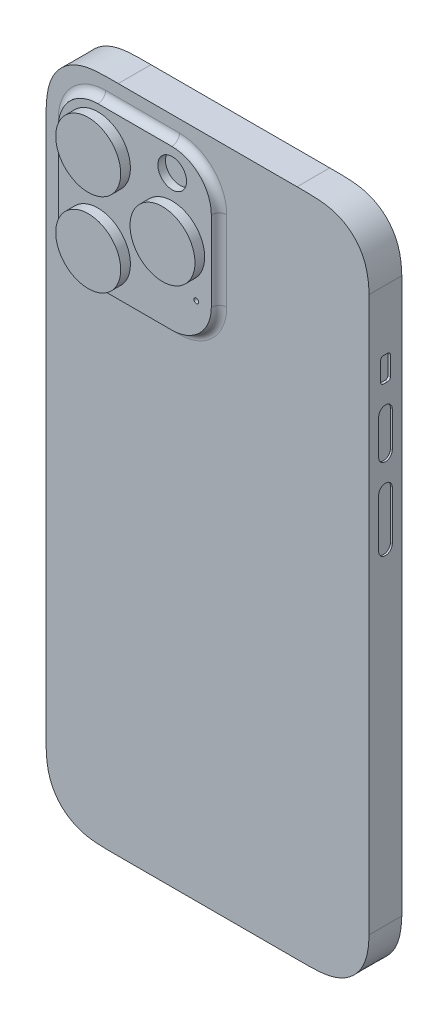
SolidWorks part; units mm, degrees
ref_plane "前视基准面" through (0, 0, 0) normal (0, 0, 1) x (1, 0, 0)
ref_plane "上视基准面" through (0, 0, 0) normal (0, 1, 0) x (1, 0, 0)
ref_plane "右视基准面" through (0, 0, 0) normal (1, 0, 0) x (0, 0, -1)
other "Configuration Table"
sketch "草图1" plane through (0, 0, 0) normal (0, 0, 1) x (1, 0, 0)
  line L0 (-34.5301, 57.507) -> (-34.5301, 50057.507) construction
  line L1 (-73.3201, 137.862) -> (4.2599, 137.862)
  line L2 (-73.3201, 137.862) -> (-73.3201, -22.848)
  line L3 (-73.3201, -22.848) -> (4.2599, -22.848)
  line L4 (4.2599, 137.862) -> (4.2599, -22.848)
  line L5 (-73.3201, 137.862) -> (4.2599, -22.848) construction
  line L6 (-73.3201, -22.848) -> (4.2599, 137.862) construction
  line L7 (-34.5301, 57.507) -> (-50034.5301, 57.507) construction
  spline S0 degree 3 poles (-73.3201, 122.312) (-73.3816, 125.2822) (-73.0975, 130.133) (-69.278, 135.1034) (-63.7712, 138.0734) (-58.9886, 137.839) (-56.0001, 137.862) knots 0 0 0 0 0.333631 0.499509 0.665643 1 1 1 1
  spline S1 degree 3 poles (4.2599, 122.312) (4.3213, 125.2822) (4.0372, 130.133) (0.2177, 135.1034) (-5.2891, 138.0734) (-10.0717, 137.839) (-13.0601, 137.862) knots 0 0 0 0 0.333631 0.499509 0.665643 1 1 1 1
  spline S2 degree 3 poles (-73.3201, -7.298) (-73.3816, -10.2683) (-73.0975, -15.119) (-69.278, -20.0894) (-63.7712, -23.0594) (-58.9886, -22.825) (-56.0001, -22.848) knots 0 0 0 0 0.333631 0.499509 0.665643 1 1 1 1
  spline S3 degree 3 poles (4.2599, -7.298) (4.3213, -10.2683) (4.0372, -15.119) (0.2177, -20.0894) (-5.2891, -23.0594) (-10.0717, -22.825) (-13.0601, -22.848) knots 0 0 0 0 0.333631 0.499509 0.665643 1 1 1 1
  point P0 (-34.5301, 57.507)
  point P8 (-34.5301, -22.848)
  dimension "D1" = 80.355
  dimension "D2" = 38.79
  dimension "D3" = 0.06
  dimension "D4" = 0.81
  dimension "D5" = 3.01
  dimension "D6" = 6.6
  dimension "D7" = 10.98
  dimension "D8" = 15.55
  dimension "D9" = 0.21
  dimension "D10" = 1.47
  dimension "D11" = 4.25
  dimension "D12" = 8.23
  dimension "D13" = 12.74
  dimension "D14" = 17.32
extrude "凸台-拉伸1" add sketch "草图1" along normal blind 7.85 contours S3 L4 S1 L1 S0 L2 S2 L3 region at (-34.5301, 57.507, 0)
sketch "草图2" plane through (0, 0, 0) normal (0, 0, 1) x (1, 0, 0)
  line L8 (3.2099, -9.0739) -> (3.2099, 124.0879)
  line L9 (-13.0601, 136.812) -> (-55.9921, 136.812)
  line L10 (-72.2701, 124.0879) -> (-72.2701, -9.0739)
  line L11 (-56.0001, -21.798) -> (-13.0682, -21.798)
  line L12 (3.2099, -9.0739) -> (3.2099, 124.0879)
  line L13 (-13.0601, 136.812) -> (-55.9921, 136.812)
  line L14 (-72.2701, 124.0879) -> (-72.2701, -9.0739)
  line L15 (-56.0001, -21.798) -> (-13.0682, -21.798)
  spline S8 degree 3 poles (-29.2466, -4019.9995) (-101.414, 29.9981) (-54.9704, -22.4333) (-9.0595, -21.7736) (-8.0573, -21.7337) (-6.0612, -21.501) (-5.0826, -21.3093) (-3.9015, -20.9066) (-3.6673, -20.8181) (-3.2033, -20.6244) (-2.973, -20.5189) (-2.2993, -20.1818) (-1.8694, -19.9282) (-1.0497, -19.3608) (-0.6602, -19.0466) (0.0745, -18.3515) (0.4109, -17.9801) (1.0253, -17.1947) (1.3034, -16.7803) (1.6761, -16.1257) (1.7933, -15.9009) (2.0092, -15.4457) (2.1083, -15.2152) (2.3817, -14.5156) (2.5321, -14.0387) (2.7815, -13.0678) (2.8807, -12.5723) (10.7356, 37.6797) (-191.2997, 108.2854) (3993.0103, -257.0084) knots -5.47769 -5.47769 -5.47769 -5.47769 0.125 0.125 0.25 0.25 0.375 0.375 0.40625 0.40625 0.4375 0.4375 0.5 0.5 0.5625 0.5625 0.625 0.625 0.6875 0.6875 0.71875 0.71875 0.75 0.75 0.8125 0.8125 0.875 0.875 7.135418 7.135418 7.135418 7.135418 only from (-13.0682, -21.798) to (3.2099, -9.0739)
  spline S9 degree 3 poles (3960.2276, 690.8908) (-194.8572, -12.8142) (10.7783, 76.533) (2.8113, 128.0401) (2.5814, 129.0045) (2.1288, 130.1799) (2.0294, 130.4142) (1.8154, 130.8709) (1.7004, 131.0942) (1.3319, 131.7492) (1.0553, 132.1662) (0.44, 132.9606) (0.0985, 133.3401) (-0.6285, 134.0332) (-1.0161, 134.349) (-1.6319, 134.779) (-1.8429, 134.915) (-2.276, 135.1729) (-2.4989, 135.295) (-3.1751, 135.6354) (-3.6378, 135.8295) (-4.5859, 136.1552) (-5.0715, 136.286) (-6.0615, 136.4956) (-6.5586, 136.573) (-8.0523, 136.7473) (-9.0524, 136.7873) (-54.9551, 137.4531) (-102.8249, 84.8062) (77.7594, 4133.9226) knots -6.328874 -6.328874 -6.328874 -6.328874 0.125 0.125 0.25 0.25 0.28125 0.28125 0.3125 0.3125 0.375 0.375 0.4375 0.4375 0.5 0.5 0.53125 0.53125 0.5625 0.5625 0.625 0.625 0.6875 0.6875 0.75 0.75 0.875 0.875 6.479402 6.479402 6.479402 6.479402 only from (3.2099, 124.0879) to (-13.0601, 136.812)
  spline S10 degree 3 poles (-39.8137, 4135.0135) (32.3537, 85.0159) (-14.0899, 137.4473) (-60.0008, 136.7875) (-61.003, 136.7477) (-62.9991, 136.515) (-63.9777, 136.3233) (-65.1588, 135.9206) (-65.393, 135.8321) (-65.857, 135.6384) (-66.0873, 135.5329) (-66.761, 135.1958) (-67.1909, 134.9422) (-68.0106, 134.3747) (-68.4001, 134.0605) (-69.1348, 133.3655) (-69.4712, 132.9941) (-70.0856, 132.2087) (-70.3637, 131.7943) (-70.7364, 131.1396) (-70.8536, 130.9149) (-71.0695, 130.4597) (-71.1686, 130.2292) (-71.442, 129.5296) (-71.5924, 129.0527) (-71.8418, 128.0818) (-71.941, 127.5863) (-79.7959, 77.3343) (122.2394, 6.7286) (-4062.0706, 372.0224) knots -5.47769 -5.47769 -5.47769 -5.47769 0.125 0.125 0.25 0.25 0.375 0.375 0.40625 0.40625 0.4375 0.4375 0.5 0.5 0.5625 0.5625 0.625 0.625 0.6875 0.6875 0.71875 0.71875 0.75 0.75 0.8125 0.8125 0.875 0.875 7.135418 7.135418 7.135418 7.135418 only from (-55.9921, 136.812) to (-72.2701, 124.0879)
  spline S11 degree 3 poles (-4029.2879, -575.8768) (125.7969, 127.8282) (-79.8386, 38.481) (-71.8716, -13.0261) (-71.6417, -13.9905) (-71.1891, -15.1659) (-71.0897, -15.4002) (-70.8757, -15.857) (-70.7607, -16.0803) (-70.3922, -16.7352) (-70.1156, -17.1522) (-69.5003, -17.9466) (-69.1588, -18.3261) (-68.4318, -19.0192) (-68.0442, -19.335) (-67.4284, -19.765) (-67.2174, -19.901) (-66.7843, -20.1589) (-66.5614, -20.281) (-65.8852, -20.6214) (-65.4224, -20.8155) (-64.4744, -21.1412) (-63.9888, -21.2721) (-62.9988, -21.4816) (-62.5017, -21.559) (-61.008, -21.7333) (-60.0079, -21.7733) (-14.1052, -22.4391) (33.7646, 30.2078) (-146.8197, -4018.9087) knots -6.328874 -6.328874 -6.328874 -6.328874 0.125 0.125 0.25 0.25 0.28125 0.28125 0.3125 0.3125 0.375 0.375 0.4375 0.4375 0.5 0.5 0.53125 0.53125 0.5625 0.5625 0.625 0.625 0.6875 0.6875 0.75 0.75 0.875 0.875 6.479402 6.479402 6.479402 6.479402 only from (-72.2701, -9.0739) to (-56.0001, -21.798)
  spline S12 degree 3 poles (-13.0682, -21.798) (-12.0661, -21.7903) (-11.0634, -21.8023) (-9.0595, -21.7736) (-8.0573, -21.7337) (-6.0612, -21.501) (-5.0826, -21.3093) (-3.9015, -20.9066) (-3.6673, -20.8181) (-3.2033, -20.6244) (-2.973, -20.5189) (-2.2993, -20.1818) (-1.8694, -19.9282) (-1.0497, -19.3608) (-0.6602, -19.0466) (0.0745, -18.3515) (0.4109, -17.9801) (1.0253, -17.1947) (1.3034, -16.7803) (1.6761, -16.1257) (1.7933, -15.9009) (2.0092, -15.4457) (2.1083, -15.2152) (2.3817, -14.5156) (2.5321, -14.0387) (2.7815, -13.0678) (2.8807, -12.5723) (3.1136, -11.0821) (3.1853, -10.0803) (3.2099, -9.0739) knots 0 0 0 0 0.125 0.125 0.25 0.25 0.375 0.375 0.40625 0.40625 0.4375 0.4375 0.5 0.5 0.5625 0.5625 0.625 0.625 0.6875 0.6875 0.71875 0.71875 0.75 0.75 0.8125 0.8125 0.875 0.875 1 1 1 1
  spline S13 degree 3 poles (3.2099, 124.0879) (3.1854, 125.0896) (3.1141, 126.0828) (2.8113, 128.0401) (2.5814, 129.0045) (2.1288, 130.1799) (2.0294, 130.4142) (1.8154, 130.8709) (1.7004, 131.0942) (1.3319, 131.7492) (1.0553, 132.1662) (0.44, 132.9606) (0.0985, 133.3401) (-0.6285, 134.0332) (-1.0161, 134.349) (-1.6319, 134.779) (-1.8429, 134.915) (-2.276, 135.1729) (-2.4989, 135.295) (-3.1751, 135.6354) (-3.6378, 135.8295) (-4.5859, 136.1552) (-5.0715, 136.286) (-6.0615, 136.4956) (-6.5586, 136.573) (-8.0523, 136.7473) (-9.0524, 136.7873) (-11.0553, 136.8164) (-12.0583, 136.8044) (-13.0601, 136.812) knots 0 0 0 0 0.125 0.125 0.25 0.25 0.28125 0.28125 0.3125 0.3125 0.375 0.375 0.4375 0.4375 0.5 0.5 0.53125 0.53125 0.5625 0.5625 0.625 0.625 0.6875 0.6875 0.75 0.75 0.875 0.875 1 1 1 1
  spline S14 degree 3 poles (-55.9921, 136.812) (-56.9942, 136.8043) (-57.9969, 136.8163) (-60.0008, 136.7875) (-61.003, 136.7477) (-62.9991, 136.515) (-63.9777, 136.3233) (-65.1588, 135.9206) (-65.393, 135.8321) (-65.857, 135.6384) (-66.0873, 135.5329) (-66.761, 135.1958) (-67.1909, 134.9422) (-68.0106, 134.3747) (-68.4001, 134.0605) (-69.1348, 133.3655) (-69.4712, 132.9941) (-70.0856, 132.2087) (-70.3637, 131.7943) (-70.7364, 131.1396) (-70.8536, 130.9149) (-71.0695, 130.4597) (-71.1686, 130.2292) (-71.442, 129.5296) (-71.5924, 129.0527) (-71.8418, 128.0818) (-71.941, 127.5863) (-72.1739, 126.0961) (-72.2456, 125.0943) (-72.2701, 124.0879) knots 0 0 0 0 0.125 0.125 0.25 0.25 0.375 0.375 0.40625 0.40625 0.4375 0.4375 0.5 0.5 0.5625 0.5625 0.625 0.625 0.6875 0.6875 0.71875 0.71875 0.75 0.75 0.8125 0.8125 0.875 0.875 1 1 1 1
  spline S15 degree 3 poles (-72.2701, -9.0739) (-72.2457, -10.0756) (-72.1744, -11.0688) (-71.8716, -13.0261) (-71.6417, -13.9905) (-71.1891, -15.1659) (-71.0897, -15.4002) (-70.8757, -15.857) (-70.7607, -16.0803) (-70.3922, -16.7352) (-70.1156, -17.1522) (-69.5003, -17.9466) (-69.1588, -18.3261) (-68.4318, -19.0192) (-68.0442, -19.335) (-67.4284, -19.765) (-67.2174, -19.901) (-66.7843, -20.1589) (-66.5614, -20.281) (-65.8852, -20.6214) (-65.4224, -20.8155) (-64.4744, -21.1412) (-63.9888, -21.2721) (-62.9988, -21.4816) (-62.5017, -21.559) (-61.008, -21.7333) (-60.0079, -21.7733) (-58.005, -21.8024) (-57.002, -21.7904) (-56.0001, -21.798) knots 0 0 0 0 0.125 0.125 0.25 0.25 0.28125 0.28125 0.3125 0.3125 0.375 0.375 0.4375 0.4375 0.5 0.5 0.53125 0.53125 0.5625 0.5625 0.625 0.625 0.6875 0.6875 0.75 0.75 0.875 0.875 1 1 1 1
  dimension "D1" = 1.05
extrude "切除-拉伸1" cut sketch "草图2" along normal blind 0.001 contours S12 L12 S13 L13 S14 L14 S15 L15
sketch "草图5" plane through (0, 0, 0) normal (0, 0, 1) x (1, 0, 0)
  line L8 (-56.0001, -18.613) -> (-13.0927, -18.6131)
  line L9 (-69.0851, 124.048) -> (-69.0851, -9.034)
  line L10 (-13.0602, 133.627) -> (-55.9676, 133.6271)
  line L11 (0.0249, -9.034) -> (0.0249, 124.048)
  line L12 (-56.0001, -18.613) -> (-13.0927, -18.6131)
  line L13 (-69.0851, 124.048) -> (-69.0851, -9.034)
  line L14 (-13.0602, 133.627) -> (-55.9676, 133.6271)
  line L15 (0.0249, -9.034) -> (0.0249, 124.048)
  spline S8 degree 3 poles (-4048.1363, -398.9785) (99.0671, 98.1446) (-75.1087, 31.6027) (-68.8413, -11.8028) (-68.7699, -12.1936) (-68.5846, -12.9696) (-68.4699, -13.3554) (-68.1899, -14.0991) (-68.023, -14.4587) (-67.625, -15.1486) (-67.3935, -15.4811) (-66.8857, -16.0919) (-66.6081, -16.3739) (-66.0012, -16.8869) (-65.6691, -17.1194) (-64.9804, -17.5224) (-64.6222, -17.6955) (-63.8797, -17.9882) (-63.4932, -18.1067) (-62.3333, -18.385) (-61.5491, -18.4789) (-59.9714, -18.5898) (-59.1772, -18.6044) (-13.5653, -18.8647) (31.3557, 15.1942) (64.0257, -4014.9279) knots -6.720849 -6.720849 -6.720849 -6.720849 0.125 0.125 0.1875 0.1875 0.25 0.25 0.3125 0.3125 0.375 0.375 0.4375 0.4375 0.5 0.5 0.5625 0.5625 0.625 0.625 0.75 0.75 0.875 0.875 7.928456 7.928456 7.928456 7.928456 only from (-69.0851, -9.034) to (-56.0001, -18.613)
  spline S9 degree 3 poles (-267.9824, 4126.1525) (34.1476, 101.67) (-13.4853, 133.8486) (-59.1098, 133.6192) (-59.8944, 133.606) (-61.4569, 133.5021) (-62.235, 133.4138) (-63.3907, 133.1489) (-63.7758, 133.0368) (-64.5324, 132.7496) (-64.8959, 132.5794) (-65.5921, 132.1835) (-65.9263, 131.9565) (-66.5518, 131.4416) (-66.836, 131.1593) (-67.3528, 130.5495) (-67.5865, 130.2213) (-67.9976, 129.5233) (-68.1694, 129.1604) (-68.4563, 128.4115) (-68.5727, 128.0245) (-68.763, 127.24) (-68.8365, 126.845) (-75.1574, 83.5753) (99.1977, 18.5223) (-4050.7998, 484.5064) knots -7.011508 -7.011508 -7.011508 -7.011508 0.125 0.125 0.25 0.25 0.375 0.375 0.4375 0.4375 0.5 0.5 0.5625 0.5625 0.625 0.625 0.6875 0.6875 0.75 0.75 0.8125 0.8125 0.875 0.875 7.627543 7.627543 7.627543 7.627543 only from (-55.9676, 133.6271) to (-69.0851, 124.048)
  spline S10 degree 3 poles (3979.076, 513.9925) (-168.1274, 16.8694) (6.0484, 83.4112) (-0.219, 126.8168) (-0.2904, 127.2076) (-0.4757, 127.9836) (-0.5904, 128.3693) (-0.8704, 129.1131) (-1.0373, 129.4727) (-1.4353, 130.1626) (-1.6668, 130.495) (-2.1746, 131.1058) (-2.4522, 131.3879) (-3.0591, 131.9009) (-3.3912, 132.1334) (-4.0799, 132.5364) (-4.4381, 132.7095) (-5.1806, 133.0022) (-5.5671, 133.1207) (-6.727, 133.399) (-7.5112, 133.4929) (-9.0889, 133.6038) (-9.8831, 133.6184) (-55.495, 133.8787) (-100.416, 99.8198) (-133.086, 4129.9419) knots -6.720849 -6.720849 -6.720849 -6.720849 0.125 0.125 0.1875 0.1875 0.25 0.25 0.3125 0.3125 0.375 0.375 0.4375 0.4375 0.5 0.5 0.5625 0.5625 0.625 0.625 0.75 0.75 0.875 0.875 7.928456 7.928456 7.928456 7.928456 only from (0.0249, 124.048) to (-13.0602, 133.627)
  spline S11 degree 3 poles (198.9221, -4011.1385) (-103.2079, 13.344) (-55.575, -18.8346) (-9.9505, -18.6052) (-9.1659, -18.592) (-7.6034, -18.4881) (-6.8253, -18.3998) (-5.6696, -18.1349) (-5.2845, -18.0228) (-4.5279, -17.7357) (-4.1644, -17.5654) (-3.4682, -17.1695) (-3.134, -16.9426) (-2.5085, -16.4276) (-2.2243, -16.1453) (-1.7075, -15.5356) (-1.4738, -15.2074) (-1.0627, -14.5093) (-0.8909, -14.1464) (-0.604, -13.3975) (-0.4876, -13.0105) (-0.2973, -12.226) (-0.2238, -11.831) (6.0971, 31.4386) (-168.258, 96.4917) (3981.7395, -369.4924) knots -7.011508 -7.011508 -7.011508 -7.011508 0.125 0.125 0.25 0.25 0.375 0.375 0.4375 0.4375 0.5 0.5 0.5625 0.5625 0.625 0.625 0.6875 0.6875 0.75 0.75 0.8125 0.8125 0.875 0.875 7.627543 7.627543 7.627543 7.627543 only from (-13.0927, -18.6131) to (0.0249, -9.034)
  spline S12 degree 3 poles (-69.0851, -9.034) (-69.0646, -9.8315) (-69.0114, -10.6247) (-68.8413, -11.8028) (-68.7699, -12.1936) (-68.5846, -12.9696) (-68.4699, -13.3554) (-68.1899, -14.0991) (-68.023, -14.4587) (-67.625, -15.1486) (-67.3935, -15.4811) (-66.8857, -16.0919) (-66.6081, -16.3739) (-66.0012, -16.8869) (-65.6691, -17.1194) (-64.9804, -17.5224) (-64.6222, -17.6955) (-63.8797, -17.9882) (-63.4932, -18.1067) (-62.3333, -18.385) (-61.5491, -18.4789) (-59.9714, -18.5898) (-59.1772, -18.6044) (-57.5887, -18.6135) (-56.7944, -18.6072) (-56.0001, -18.613) knots 0 0 0 0 0.125 0.125 0.1875 0.1875 0.25 0.25 0.3125 0.3125 0.375 0.375 0.4375 0.4375 0.5 0.5 0.5625 0.5625 0.625 0.625 0.75 0.75 0.875 0.875 1 1 1 1
  spline S13 degree 3 poles (-55.9676, 133.6271) (-56.7528, 133.6211) (-57.539, 133.6271) (-59.1098, 133.6192) (-59.8944, 133.606) (-61.4569, 133.5021) (-62.235, 133.4138) (-63.3907, 133.1489) (-63.7758, 133.0368) (-64.5324, 132.7496) (-64.8959, 132.5794) (-65.5921, 132.1835) (-65.9263, 131.9565) (-66.5518, 131.4416) (-66.836, 131.1593) (-67.3528, 130.5495) (-67.5865, 130.2213) (-67.9976, 129.5233) (-68.1694, 129.1604) (-68.4563, 128.4115) (-68.5727, 128.0245) (-68.763, 127.24) (-68.8365, 126.845) (-69.0104, 125.6546) (-69.0644, 124.8533) (-69.0851, 124.048) knots 0 0 0 0 0.125 0.125 0.25 0.25 0.375 0.375 0.4375 0.4375 0.5 0.5 0.5625 0.5625 0.625 0.625 0.6875 0.6875 0.75 0.75 0.8125 0.8125 0.875 0.875 1 1 1 1
  spline S14 degree 3 poles (0.0249, 124.048) (0.0043, 124.8455) (-0.0489, 125.6387) (-0.219, 126.8168) (-0.2904, 127.2076) (-0.4757, 127.9836) (-0.5904, 128.3693) (-0.8704, 129.1131) (-1.0373, 129.4727) (-1.4353, 130.1626) (-1.6668, 130.495) (-2.1746, 131.1058) (-2.4522, 131.3879) (-3.0591, 131.9009) (-3.3912, 132.1334) (-4.0799, 132.5364) (-4.4381, 132.7095) (-5.1806, 133.0022) (-5.5671, 133.1207) (-6.727, 133.399) (-7.5112, 133.4929) (-9.0889, 133.6038) (-9.8831, 133.6184) (-11.4716, 133.6274) (-12.2659, 133.6212) (-13.0602, 133.627) knots 0 0 0 0 0.125 0.125 0.1875 0.1875 0.25 0.25 0.3125 0.3125 0.375 0.375 0.4375 0.4375 0.5 0.5 0.5625 0.5625 0.625 0.625 0.75 0.75 0.875 0.875 1 1 1 1
  spline S15 degree 3 poles (-13.0927, -18.6131) (-12.3075, -18.6071) (-11.5213, -18.6131) (-9.9505, -18.6052) (-9.1659, -18.592) (-7.6034, -18.4881) (-6.8253, -18.3998) (-5.6696, -18.1349) (-5.2845, -18.0228) (-4.5279, -17.7357) (-4.1644, -17.5654) (-3.4682, -17.1695) (-3.134, -16.9426) (-2.5085, -16.4276) (-2.2243, -16.1453) (-1.7075, -15.5356) (-1.4738, -15.2074) (-1.0627, -14.5093) (-0.8909, -14.1464) (-0.604, -13.3975) (-0.4876, -13.0105) (-0.2973, -12.226) (-0.2238, -11.831) (-0.0499, -10.6406) (0.0041, -9.8393) (0.0249, -9.034) knots 0 0 0 0 0.125 0.125 0.25 0.25 0.375 0.375 0.4375 0.4375 0.5 0.5 0.5625 0.5625 0.625 0.625 0.6875 0.6875 0.75 0.75 0.8125 0.8125 0.875 0.875 1 1 1 1
  dimension "D1" = 3.185
extrude "切除-拉伸2" cut sketch "草图5" along normal blind 0.01
sketch "草图6" plane through (0, 0, 0) normal (0, 0, 1) x (1, 0, 0)
  line L1 (-28.5457, 136.967) -> (-42.7557, 136.967)
  line L2 (-28.5457, 136.967) -> (-28.5457, 136.592)
  line L3 (-28.9207, 136.217) -> (-42.3807, 136.217)
  line L4 (-42.7557, 136.967) -> (-42.7557, 136.592)
  line L5 (-28.5457, 136.967) -> (-42.7557, 136.217) construction
  line L6 (-28.5457, 136.217) -> (-42.7557, 136.967) construction
  line L7 (-56.0001, 137.862) -> (-13.0601, 137.862) construction
  arc A0 (-42.3807, 136.217) -> (-42.7557, 136.592) centre (-42.3807, 136.592) cw
  arc A1 (-28.5457, 136.592) -> (-28.9207, 136.217) centre (-28.9207, 136.592) cw
  point P0 (-35.6507, 136.592)
  dimension "D4" = 0.375
  dimension "D1" = 1.27
  dimension "D2" = 0.75
  dimension "D3" = 14.21
extrude "切除-拉伸3" cut sketch "草图6" along normal blind 0.1
sketch "草图7" plane through (0, 0, 0) normal (0, 0, 1) x (1, 0, 0)
  line L0 (-24.3777, 129.762) -> (-45.1377, 129.762) construction
  line L1 (-24.3777, 126.727) -> (-45.1377, 126.727)
  line L2 (-24.3777, 132.797) -> (-45.1377, 132.797)
  line L3 (-56.0001, 137.862) -> (-13.0601, 137.862) construction
  arc A0 (-24.3777, 126.727) -> (-24.3777, 132.797) centre (-24.3777, 129.762) ccw
  arc A1 (-45.1377, 132.797) -> (-45.1377, 126.727) centre (-45.1377, 129.762) ccw
  point P2 (-34.7577, 129.762)
  dimension "D1" = 20.76
  dimension "D2" = 8.1
  dimension "D3" = 6.07
sketch "草图8" plane through (0, -22.848, 0) normal (0, -1, 0) x (1, 0, 0)
  line L0 (-73.3201, 3.925) -> (9.9623, 3.925) construction
  line L1 (-73.3201, 7.85) -> (-73.3201, 0) construction
  line L2 (-37.3801, 3.925) -> (-32.3173, 3.925) construction
  line L3 (-37.3801, 5.475) -> (-32.3173, 5.475)
  line L4 (-37.3801, 2.375) -> (-32.3173, 2.375)
  circle A1 centre (-54.2101, 3.925) radius 0.765
  circle A2 centre (-51.9351, 3.925) radius 0.765
  circle A3 centre (-49.6601, 3.925) radius 0.765
  circle A4 centre (-47.3851, 3.925) radius 0.765
  circle A5 centre (-23.9501, 3.925) radius 0.765
  circle A6 centre (-21.3901, 3.925) radius 0.765
  circle A7 centre (-18.8301, 3.925) radius 0.765
  circle A8 centre (-16.2701, 3.925) radius 0.765
  circle A9 centre (-13.7101, 3.925) radius 0.765
  circle A10 centre (-11.1501, 3.925) radius 0.765
  circle A11 centre (-40.9301, 3.925) radius 0.7525
  arc A12 (-37.3801, 5.475) -> (-37.3801, 2.375) centre (-37.3801, 3.925) ccw
  arc A13 (-32.3173, 2.375) -> (-32.3173, 5.475) centre (-32.3173, 3.925) ccw
  circle A14 centre (-28.7673, 3.925) radius 0.75
  point P28 (-34.8487, 3.925)
  point P36 (-38.9301, 3.925)
  point P37 (-30.7673, 3.925)
  dimension "D1" = 19.11
  dimension "D4" = 1.53
  dimension "D7" = 62.17
  dimension "D8" = 2
  dimension "D9" = 2
  dimension "D3" = 2.275
  dimension "D5" = 49.37
  dimension "D12" = 32.39
  dimension "D2" = 4
  dimension "D6" = 6
extrude "切除-拉伸5" cut sketch "草图8" against normal blind 3
sketch "草图10" plane through (0, 0, 7.85) normal (0, 0, 1) x (1, 0, 0)
  line L0 (-73.3201, 124.1006) -> (-73.3201, -9.0866) construction
  line L1 (-59.0401, 133.072) -> (-41.2901, 133.072)
  line L2 (-68.5301, 123.582) -> (-68.5301, 104.342)
  line L3 (-59.0401, 94.852) -> (-41.2901, 94.852)
  line L4 (-31.8001, 123.582) -> (-31.8001, 104.342)
  line L5 (-68.5301, 133.072) -> (-31.8001, 94.852) construction
  line L6 (-68.5301, 94.852) -> (-31.8001, 133.072) construction
  line L7 (-56.0001, 137.862) -> (-13.0601, 137.862) construction
  arc A0 (-41.2901, 94.852) -> (-31.8001, 104.342) centre (-41.2901, 104.342) ccw
  arc A1 (-68.5301, 104.342) -> (-59.0401, 94.852) centre (-59.0401, 104.342) ccw
  arc A2 (-41.2901, 133.072) -> (-31.8001, 123.582) centre (-41.2901, 123.582) cw
  arc A3 (-59.0401, 133.072) -> (-68.5301, 123.582) centre (-59.0401, 123.582) ccw
  circle A4 centre (-41.2001, 127.542) radius 3.45
  circle A5 centre (-35.4101, 103.882) radius 0.575
  point P0 (-50.1651, 113.962)
  dimension "D5" = 9.49
  dimension "D6" = 32.12
  dimension "D7" = 10.32
  dimension "D8" = 6.9
  dimension "D9" = 1.15
  dimension "D1" = 41.52
  dimension "D2" = 43.01
  dimension "D3" = 4.79
  dimension "D4" = 4.79
  dimension "D10" = 37.91
  dimension "D11" = 33.98
extrude "凸台-拉伸2" add sketch "草图10" along normal blind 1.85
sketch "草图11" plane through (0, 0, 7.85) normal (0, 0, 1) x (1, 0, 0)
  line L0 (-73.3201, 124.1006) -> (-73.3201, -9.0866) construction
  line L1 (-56.0001, 137.862) -> (-13.0601, 137.862) construction
  circle A0 centre (-59.0401, 123.582) radius 7.805
  circle A1 centre (-59.0401, 103.5707) radius 7.805
  circle A2 centre (-41.2001, 113.962) radius 7.805
  dimension "D1" = 15.61
  dimension "D2" = 15.61
  dimension "D3" = 15.61
  dimension "D4" = 32.12
  dimension "D5" = 23.9
extrude "凸台-拉伸3" add sketch "草图11" along normal blind 4.18
fillet "圆角1" radius 1.85 8 edges at (-31.8001, 113.962, 7.85) (-34.5797, 97.6316, 7.85) (-50.1651, 94.852, 7.85) (-65.7506, 97.6316, 7.85) (-68.5301, 113.962, 7.85) (-65.7506, 130.2924, 7.85) (-50.1651, 133.072, 7.85) (-34.5797, 130.2924, 7.85)
sketch "草图12" plane through (-73.3201, 0, 0) normal (-1, 0, 0) x (0, 0, 1)
  line L0 (3.89, 91.472) -> (3.89, 73.172) construction
  line L1 (5.52, 91.472) -> (5.52, 73.172)
  line L2 (2.26, 91.472) -> (2.26, 73.172)
  line L3 (3.89, 82.322) -> (3.925, 124.1006) construction
  line L4 (7.85, 124.1006) -> (0, 124.1006) construction
  line L5 (3.925, 124.1006) -> (3.925, -9.0866) construction
  line L6 (7.85, -9.0866) -> (0, -9.0866) construction
  line L7 (7.85, 137.862) -> (0, 137.862) construction
  line L8 (7.85, 124.1006) -> (7.85, -9.0866) construction
  arc A0 (5.52, 91.472) -> (2.26, 91.472) centre (3.89, 91.472) ccw
  arc A1 (2.26, 73.172) -> (5.52, 73.172) centre (3.89, 73.172) ccw
  point P2 (3.89, 82.322)
  dimension "D2" = 9.15
  dimension "D1" = 55.54
  dimension "D3" = 3.26
  dimension "D4" = 3.96
extrude "切除-拉伸6" cut sketch "草图12" against normal blind 0.45
sketch "草图13" plane through (4.2599, 0, 0) normal (1, 0, 0) x (0, 0, -1)
  line L0 (-7.85, 137.862) -> (0, 137.862) construction
  line L1 (-4.45, 109.682) -> (-3.4, 109.682)
  line L2 (-5.1, 109.032) -> (-5.1, 104.412)
  line L3 (-4.45, 103.762) -> (-3.4, 103.762)
  line L4 (-2.75, 109.032) -> (-2.75, 104.412)
  line L5 (-5.1, 109.682) -> (-2.75, 103.762) construction
  line L6 (-5.1, 103.762) -> (-2.75, 109.682) construction
  line L7 (-3.925, 106.722) -> (-3.925, 124.1006) construction
  line L8 (-7.85, 124.1006) -> (0, 124.1006) construction
  arc A0 (-3.4, 109.682) -> (-2.75, 109.032) centre (-3.4, 109.032) cw
  arc A1 (-5.1, 104.412) -> (-4.45, 103.762) centre (-4.45, 104.412) ccw
  arc A2 (-4.45, 109.682) -> (-5.1, 109.032) centre (-4.45, 109.032) ccw
  arc A3 (-3.4, 103.762) -> (-2.75, 104.412) centre (-3.4, 104.412) ccw
  point P0 (-3.925, 106.722)
  dimension "D4" = 0.65
  dimension "D1" = 2.35
  dimension "D2" = 2.96
  dimension "D3" = 31.14
extrude "切除-拉伸7" cut sketch "草图13" against normal blind 0.6
sketch "草图14" plane through (4.2599, 0, 0) normal (1, 0, 0) x (0, 0, -1)
  line L4 (0.2, -9.2866) -> (0.2, 124.3006)
  line L5 (0.2, 124.3006) -> (-8.05, 124.3006)
  line L6 (-8.05, 124.3006) -> (-8.05, -9.2866)
  line L7 (-8.05, -9.2866) -> (0.2, -9.2866)
  line L8 (0.1, -9.1866) -> (0.1, 124.2006)
  line L9 (0.1, 124.2006) -> (-7.95, 124.2006)
  line L10 (-7.95, 124.2006) -> (-7.95, -9.1866)
  line L11 (-7.95, -9.1866) -> (0.1, -9.1866)
  line L12 (0.1, -9.1866) -> (0.1, 124.2006)
  line L13 (0.1, 124.2006) -> (-7.95, 124.2006)
  line L14 (-7.95, 124.2006) -> (-7.95, -9.1866)
  line L15 (-7.95, -9.1866) -> (0.1, -9.1866)
  line L16 (0.2, -9.1866) -> (0.2, 124.3006)
  line L17 (0.2, 124.3006) -> (-8.05, 124.3006)
  line L18 (-8.05, 124.3006) -> (-8.05, -9.1866)
  line L20 (-3.4, 109.582) -> (-3.4, 103.862) construction
  line L21 (-2.85, 104.412) -> (-2.85, 109.032)
  line L22 (-2.85, 104.412) -> (-2.85, 109.032)
  line L23 (-3.95, 104.412) -> (-3.95, 109.032)
  arc A3 (-3.4, 103.862) -> (-2.85, 104.412) centre (-3.4, 104.412) ccw
  arc A4 (-3.95, 104.412) -> (-2.85, 104.412) centre (-3.4, 104.412) ccw
  arc A6 (-2.85, 109.032) -> (-3.4, 109.582) centre (-3.4, 109.032) ccw
  arc A7 (-2.85, 109.032) -> (-3.95, 109.032) centre (-3.4, 109.032) ccw
  dimension "D1" = 0.1
  dimension "D2" = 0.1
  dimension "D3" = 0.1
  dimension "D4" = 0.1
  dimension "D5" = 0.1
  dimension "D6" = 0.1
sketch "草图15" plane through (4.2599, 0, 0) normal (1, 0, 0) x (0, 0, -1)
  line L0 (-3.925, 124.3006) -> (-3.925, -9.2866) construction
  line L1 (0.2, 124.3006) -> (-8.05, 124.3006) construction
  line L2 (-8.05, -9.2866) -> (0.2, -9.2866) construction
  line L3 (-3.925, 97.542) -> (-3.925, 89.002) construction
  line L4 (-2.295, 97.542) -> (-2.295, 89.002)
  line L5 (-5.555, 97.542) -> (-5.555, 89.002)
  line L6 (-3.925, 81.272) -> (-3.925, 69.472) construction
  line L9 (-7.85, 137.862) -> (0, 137.862) construction
  line L10 (-2.295, 81.272) -> (-2.295, 69.472)
  line L11 (-29.5456, 136.4352) -> (-29.5037, 136.4352)
  line L12 (-29.5456, 136.4352) -> (-29.5456, 136.7474)
  line L13 (-29.5456, 136.7474) -> (-29.5037, 136.7474)
  line L14 (-29.5037, 136.4352) -> (-29.5037, 136.7474)
  line L15 (-17.2793, 136.5913) -> (-18.0157, 136.5913)
  line L16 (-17.2793, 136.5913) -> (-17.2793, 138.1235)
  line L17 (-17.2793, 138.1235) -> (-18.0157, 138.1235)
  line L18 (-18.0157, 136.5913) -> (-18.0157, 138.1235)
  line L19 (-5.555, 81.272) -> (-5.555, 69.472)
  arc A0 (-2.295, 97.542) -> (-5.555, 97.542) centre (-3.925, 97.542) ccw
  arc A1 (-5.555, 89.002) -> (-2.295, 89.002) centre (-3.925, 89.002) ccw
  arc A4 (-2.295, 81.272) -> (-5.555, 81.272) centre (-3.925, 81.272) ccw
  arc A5 (-5.555, 69.472) -> (-2.295, 69.472) centre (-3.925, 69.472) ccw
  point P8 (-3.925, 93.272)
  point P15 (-3.925, 75.372)
  point P22 (-3.925, 99.172)
  point P31 (-2.295, 75.372)
  dimension "D5" = 5.9
  dimension "D6" = 12
  dimension "D4" = 5.9
  dimension "D1" = 44.59
  dimension "D2" = 3.26
  dimension "D3" = 3.26
extrude "切除-拉伸8" cut sketch "草图15" against normal blind 0.45
